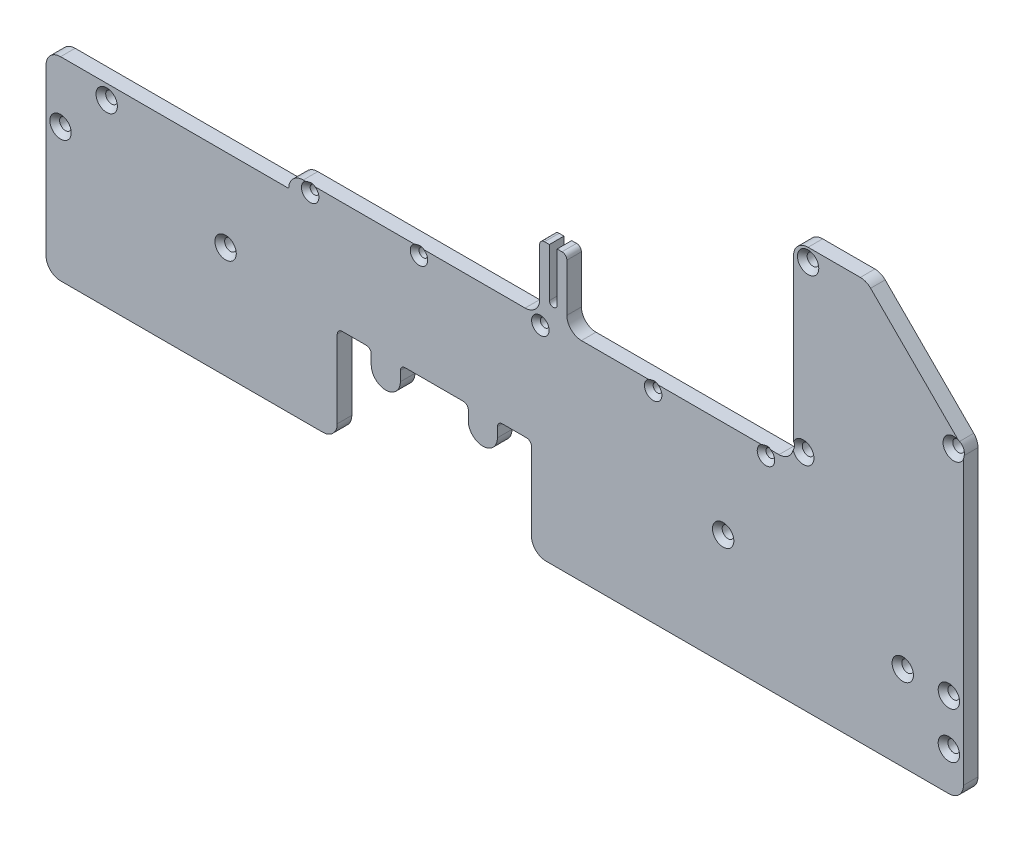
SolidWorks part; units mm, degrees
material "3.1355 (EN-AW 2024)"
ref_plane "Спереди" through (0, 0, 0) normal (0, 0, 1) x (1, 0, 0)
ref_plane "Сверху" through (0, 0, 0) normal (0, 1, 0) x (1, 0, 0)
ref_plane "Справа" through (0, 0, 0) normal (1, 0, 0) x (0, 0, -1)
sketch "Model" plane through (0, 0, 0) normal (0, 0, 1) x (1, 0, 0)
  line L1 (0, 20) -> (50, 20)
  line L2 (50, 20) -> (50, 23)
  line L11 (154, 23) -> (154, 0)
  line L19 (0, 0) -> (0, 20)
  line L54 (0, 0) -> (0, -20)
  line L55 (0, -20) -> (60, -20)
  line L56 (60, -20) -> (60, 0)
  line L57 (60, 0) -> (154, 0)
  line L60 (50, 23) -> (154, 23)
  dimension "D3" = 23
  dimension "D15" = 20
  dimension "D9" = 20
  dimension "D5" = 50
  dimension "D18" = 154
  dimension "D22" = 60
extrude "База" add sketch "Model" against normal blind 3
sketch "Эскиз14" plane through (0, 0, 0) normal (0, 0, 1) x (1, 0, 0)
  line L0 (60, 0) -> (154, 0) construction
  line L1 (67, 0) -> (73, 0)
  line L2 (67, 0) -> (67, -6)
  line L3 (67, -6) -> (73, -6)
  line L4 (73, 0) -> (73, -6)
  line L5 (60, -20) -> (60, 0) construction
  line L6 (87, 0) -> (93, 0)
  line L7 (87, 0) -> (87, -6)
  line L8 (87, -6) -> (93, -6)
  line L9 (93, 0) -> (93, -6)
  point P10 (70, -6)
  point P12 (90, -6)
  dimension "D1" = 6
  dimension "D2" = 10
  dimension "D3" = 20
extrude "Вставка в профиль 20*40" add sketch "Эскиз14" against normal up to surface (3 mm away) up to face at (66, 5.75, -3)
sketch "Эскиз15" plane through (0, 0, 0) normal (0, 0, 1) x (1, 0, 0)
  line L0 (101.7, 23) -> (101.7, 36.84)
  line L2 (154, 23) -> (50, 23) construction
  line L3 (101.7, 36.84) -> (103.7, 36.84)
  line L4 (103.7, 36.84) -> (103.7, 26.84)
  line L6 (105.3, 26.84) -> (105.3, 36.84)
  line L7 (105.3, 36.84) -> (107.3, 36.84)
  line L8 (107.3, 36.84) -> (107.3, 23)
  line L9 (107.3, 23) -> (101.7, 23)
  arc A0 (103.7, 26.84) -> (105.3, 26.84) centre (104.5, 26.84) ccw
  point P18 (104.5, 23)
  dimension "D1" = 1.6
  dimension "D2" = 5.6
  dimension "D3" = 10
  dimension "D4" = 36.84
  dimension "D6" = 104.5
extrude "Зажим датчика" add sketch "Эскиз15" against normal up to surface (3 mm away) up to face at (73, 1.375, -3)
sketch "Эскиз8" plane through (0, 0, 0) normal (0, 0, 1) x (1, 0, 0)
  line L0 (154, 23) -> (154, 63)
  line L1 (154, 63) -> (169, 63)
  line L2 (169, 63) -> (189, 43)
  line L3 (189, 43) -> (189, -20)
  line L6 (100, 0) -> (154, 0)
  line L7 (154, 0) -> (154, 23)
  line L8 (100, 0) -> (100, -20)
  line L12 (100, -20) -> (189, -20)
  line L13 (60, -20) -> (60, 0) construction
  dimension "D1" = 40
  dimension "D2" = 15
  dimension "D3" = 135
  dimension "D4" = 35
  dimension "D5" = 20
  dimension "D8" = 40
extrude "Панель управления" add sketch "Эскиз8" against normal up to surface (3 mm away) up to face at (83.5, 11.1767, -3)
fillet "Скругление5" radius 1 8 edges at (100, 0, -1.5) (93, 0, -1.5) (87, 0, -1.5) (73, 0, -1.5) (67, 0, -1.5) (60, 0, -1.5) (107.3, 36.84, -1.5) (101.7, 36.84, -1.5)
hole_wizard "Крепление M2" positions "Эскиз9" profile "Эскиз10" countersink size "M2" standard "DIN" end condition through all
sketch "Эскиз9" plane through (0, 0, 0) normal (0, 0, 1) x (1, 0, 0)
  point P0 (3, 7.5)
  point P3 (12.5, 17)
  point P18 (156, 25.95)
  point P27 (176.5, -2.5)
  point P30 (186, -12)
  point P33 (186, -2.5)
  point P36 (157, 60.32)
  point P40 (187, 42.08)
  dimension "D1" = 3
  dimension "D2" = 7.5
  dimension "D3" = 17
  dimension "D4" = 12.5
sketch "Эскиз10" plane through (3, 7.5, 0) normal (1, 0, 0) x (0, -1, 0)
  line L0 (0, 0) -> (0, 3)
  line L1 (0, 3) -> (1.2, 3)
  line L2 (1.2, 3) -> (1.2, 1)
  line L3 (1.2, 1) -> (2.2, 0)
  line L5 (2.2, 0) -> (0, 0)
  line L6 (-1.2, 1) -> (-2.2, 0) construction
  line L11 (0, -6.35) -> (0, 107.95) construction
  dimension "Диаметр сквозного отверстия" = 2.4
  dimension "Глубина сквозного отверстия" = 3
  dimension "Диаметр передней зенковки" = 4.4
  dimension "Угол передней зенковки" = 90
hole_wizard "Зенковка для винта M1.6" positions "Эскиз16" profile "Эскиз17" countersink size "M1.6" standard "ISO" end condition through all
sketch "Эскиз16" plane through (0, 0, 0) normal (0, 0, 1) x (1, 0, 0)
  line L0 (50, 20) -> (0, 20) construction
  point P0 (148.32, 21.5)
  point P3 (125.08, 21.5)
  point P6 (101.84, 21.5)
  point P9 (76.84, 21.5)
  point P12 (54.42, 21.5)
  dimension "D1" = 1.5
  dimension "D2" = 22.42
  dimension "D3" = 25
  dimension "D4" = 23.24
  dimension "D5" = 23.24
  dimension "D6" = 54.42
sketch "Эскиз17" plane through (148.32, 21.5, 0) normal (1, 0, 0) x (0, -1, 0)
  line L0 (0, 0) -> (0, 3)
  line L1 (0, 3) -> (0.9, 3)
  line L2 (0.9, 3) -> (0.9, 0.9)
  line L3 (0.9, 0.9) -> (1.8, 0)
  line L5 (1.8, 0) -> (0, 0)
  line L6 (-0.9, 0.9) -> (-1.8, 0) construction
  line L11 (0, -6.35) -> (0, 107.95) construction
  dimension "Диаметр сквозного отверстия" = 1.8
  dimension "Глубина сквозного отверстия" = 3
  dimension "Диаметр передней зенковки" = 3.6
  dimension "Угол передней зенковки" = 90
fillet "Скругление4" radius 3 12 edges at (0, 20, -1.5) (50, 23, -1.5) (154, 23, -1.5) (154, 63, -1.5) (169, 63, -1.5) (189, 43, -1.5) (107.3, 23, -1.5) (101.7, 23, -1.6467) (60, -20, -1.5) (189, -20, -1.5) (0, -20, -1.5) (100, -20, -1.5)
fillet "Скругление6" 2 edges at (67, -6, -1.5) (73, -6, -1.5) type full round first side face at (67, -3.5, -1.5) second side face at (73, -3.5, -1.5) middle face at (70, -6, -1.5)
fillet "Скругление7" 2 edges at (93, -6, -1.5) (87, -6, -1.5) type full round first side face at (93, -3.5, -1.5) second side face at (87, -3.5, -1.5) middle face at (90, -6, -1.5)
hole_wizard "УровеньПрижима-M2" positions "Эскиз18" profile "Эскиз19" countersink size "M2" standard "DIN" end condition through all
sketch "Эскиз18" plane through (0, 0, 0) normal (0, 0, 1) x (1, 0, 0)
  point P0 (37, 2.95)
  point P9 (139.5, 2.95)
  dimension "D2" = 102.5
  dimension "D3" = 37
  dimension "D4" = 2.95
sketch "Эскиз19" plane through (37, 2.95, 0) normal (1, 0, 0) x (0, -1, 0)
  line L0 (0, 0) -> (0, 3)
  line L1 (0, 3) -> (1.2, 3)
  line L2 (1.2, 3) -> (1.2, 1)
  line L3 (1.2, 1) -> (2.2, 0)
  line L5 (2.2, 0) -> (0, 0)
  line L6 (-1.2, 1) -> (-2.2, 0) construction
  line L11 (0, -6.35) -> (0, 107.95) construction
  dimension "Диаметр сквозного отверстия" = 2.4
  dimension "Глубина сквозного отверстия" = 3
  dimension "Диаметр передней зенковки" = 4.4
  dimension "Угол передней зенковки" = 90
